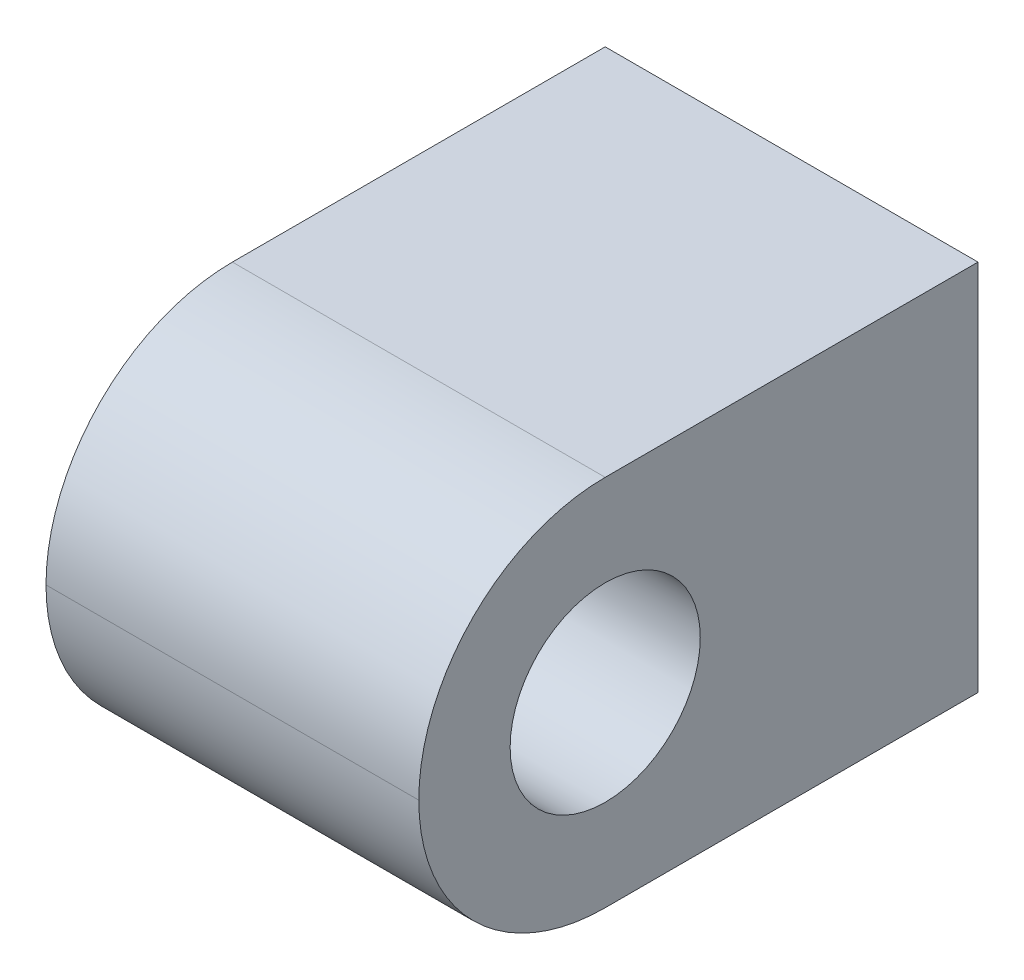
SolidWorks part; units mm, degrees
ref_plane "Front Plane" through (0, 0, 0) normal (0, 0, 1) x (1, 0, 0)
ref_plane "Top Plane" through (0, 0, 0) normal (0, 1, 0) x (1, 0, 0)
ref_plane "Right Plane" through (0, 0, 0) normal (1, 0, 0) x (0, 0, -1)
sketch "Sketch1" plane through (0, 0, 0) normal (0, 0, 1) x (1, 0, 0)
  line L1 (-5, -5) -> (5, -5)
  line L2 (-5, -5) -> (-5, 5)
  line L3 (-5, 5) -> (5, 5)
  line L4 (5, -5) -> (5, 5)
  line L5 (-5, -5) -> (5, 5) construction
  line L6 (-5, 5) -> (5, -5) construction
  circle A0 centre (0, 0) radius 2.475
  dimension "D1" = 4.95
  dimension "D2" = 10
extrude "Boss-Extrude2" add sketch "Sketch1" along normal blind 15 separate body contours A0 | L1 L4 L3 L2 A0 | A0 | L2 L1 L4 L3 region at (-4.8586, 0, 0) region at (0, 0, 0)
sketch "Sketch2" plane through (-5, 0, 0) normal (-1, 0, 0) x (0, 0, 1)
  line L0 (15, 5) -> (15, -5) construction
  circle A0 centre (10, 0) radius 2.55
  dimension "D1" = 5.1
  dimension "D2" = 5
extrude "Cut-Extrude1" cut sketch "Sketch2" against normal blind 10
fillet "Fillet1" radius 5 2 edges at (0, -5, 15) (0, 5, 15)
extrude "Cut-Extrude2" cut sketch "Sketch1<5>" along normal blind 7 contours A0 region at (0, 0, 0)
sketch "Sketch1<5>" plane through (0, 0, 0) normal (0, 0, 1) x (1, 0, 0) same geometry as "Sketch1"
